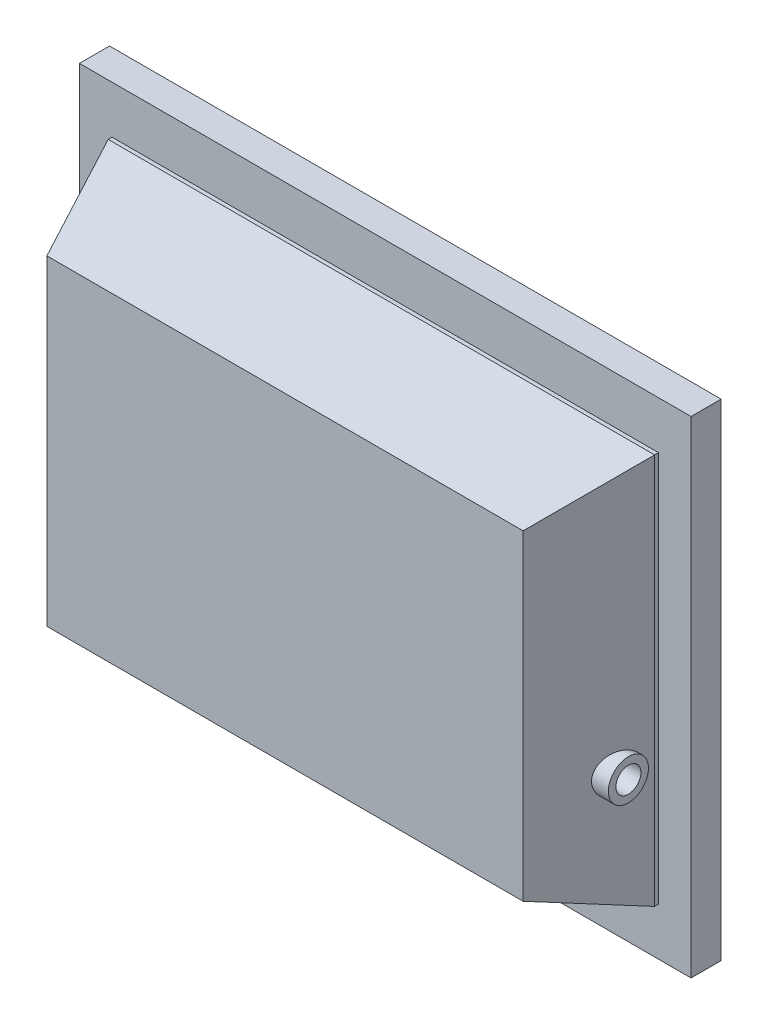
SolidWorks part; units mm, degrees
ref_plane "Ebene vorne" through (0, 0, 0) normal (0, 0, 1) x (1, 0, 0)
ref_plane "Ebene oben" through (0, 0, 0) normal (0, 1, 0) x (1, 0, 0)
ref_plane "Ebene rechts" through (0, 0, 0) normal (1, 0, 0) x (0, 0, -1)
sketch "Skizze1" plane through (0, 0, 0) normal (0, 0, 1) x (1, 0, 0)
  line L1 (-61, -48.5) -> (61, -48.5)
  line L2 (-61, -48.5) -> (-61, 48.5)
  line L3 (-61, 48.5) -> (61, 48.5)
  line L4 (61, -48.5) -> (61, 48.5)
  line L5 (-61, -48.5) -> (61, 48.5) construction
  line L6 (-61, 48.5) -> (61, -48.5) construction
  point P0 (0, 0)
  dimension "D1" = 97
  dimension "D2" = 122
extrude "Aufsatz-Linear austragen1" add sketch "Skizze1" along normal blind 6
sketch "Skizze2" plane through (0, 0, 6) normal (0, 0, 1) x (1, 0, 0)
  line L1 (-54.5, -39) -> (54.5, -39)
  line L2 (-54.5, -39) -> (-54.5, 39)
  line L3 (-54.5, 39) -> (54.5, 39)
  line L4 (54.5, -39) -> (54.5, 39)
  line L5 (-54.5, -39) -> (54.5, 39) construction
  line L6 (-54.5, 39) -> (54.5, -39) construction
  point P0 (0, 0)
  dimension "D1" = 109
  dimension "D2" = 78
extrude "Aufsatz-Linear austragen2" add sketch "Skizze2" along normal blind 20
sketch "Skizze3" plane through (54.5, 0, 0) normal (1, 0, 0) x (0, 0, -1)
  line L0 (0, -48.5) -> (0, 48.5) construction
  line L1 (-6, -48.5) -> (0, -48.5) construction
  circle A0 centre (-12, -14.5) radius 2.5
  dimension "D3" = 5
  dimension "D1" = 12
  dimension "D2" = 34
extrude "Schnitt-Linear austragen1" cut sketch "Skizze3" against normal up to next
chamfer "Fase1" distance 7 angle 70 4 edges at (0, 39, 26) (54.5, 0, 26) (0, -39, 26) (-54.5, 0, 26) first distance on face at (0, 0, 26)
sketch "Skizze4" plane through (54.5, 0, 0) normal (1, 0, 0) x (0, 0, -1)
  circle A0 centre (-12, -14.5) radius 2.5
  circle A1 centre (-12, -14.5) radius 4
  dimension "D1" = 8
extrude "Aufsatz-Linear austragen3" add sketch "Skizze4" against normal up to surface (109 mm away) up to face at (-54.5, 0, 6.3838)
sketch "Skizze5" plane through (0, 0, 0) normal (0, 0, -1) x (-1, 0, 0)
  line L1 (46.2409, 34.6821) -> (-46.2409, 34.6821)
  line L2 (46.2409, 34.6821) -> (46.2409, -34.6821)
  line L3 (46.2409, -34.6821) -> (-46.2409, -34.6821)
  line L4 (-46.2409, 34.6821) -> (-46.2409, -34.6821)
  line L5 (46.2409, 34.6821) -> (-46.2409, -34.6821) construction
  line L6 (46.2409, -34.6821) -> (-46.2409, 34.6821) construction
  point P0 (0, 0)
extrude "Schnitt-Linear austragen2" cut sketch "Skizze5" against normal blind 1
